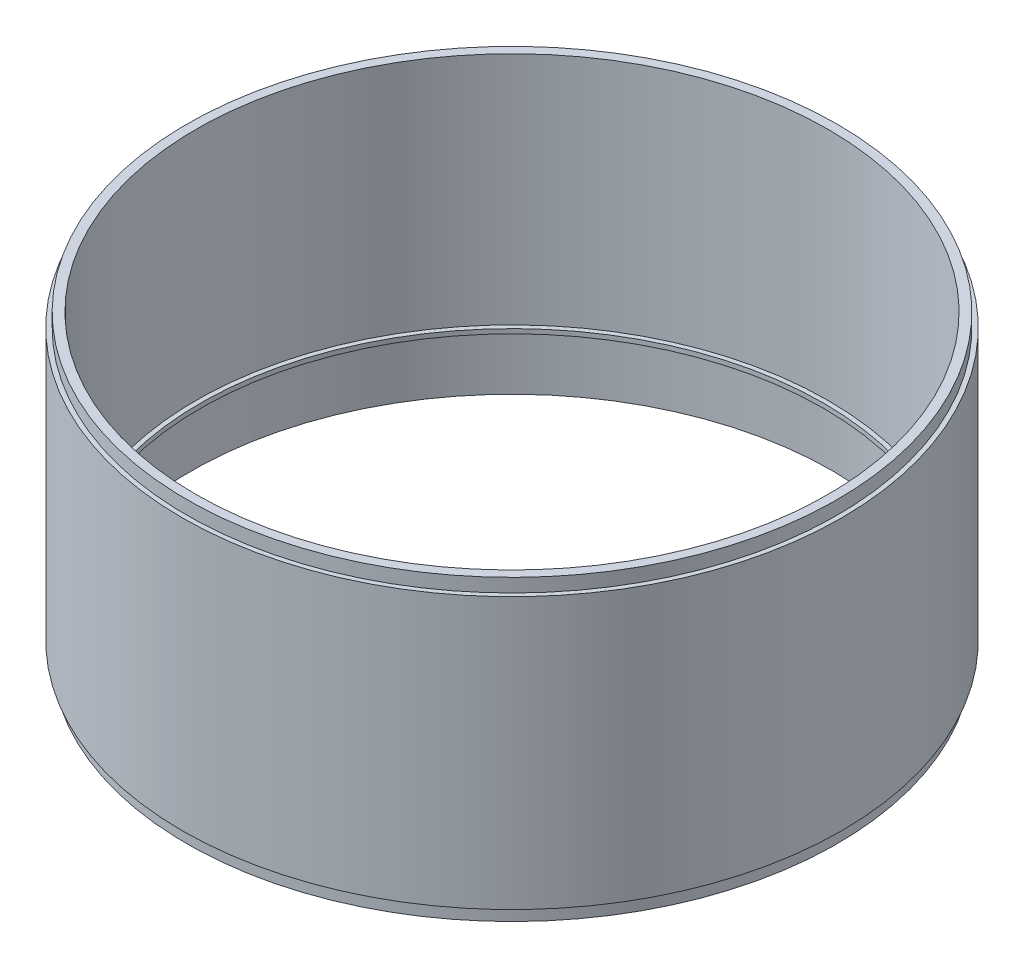
SolidWorks part; units mm, degrees
material "Silica Phenolic"
ref_plane "Piano frontale" through (0, 0, 0) normal (0, 0, 1) x (1, 0, 0)
ref_plane "Piano superiore" through (0, 0, 0) normal (0, 1, 0) x (1, 0, 0)
ref_plane "Piano destro" through (0, 0, 0) normal (1, 0, 0) x (0, 0, -1)
sketch "Schizzo1" plane through (0, 0, 0) normal (0, 0, 1) x (1, 0, 0)
  line L0 (-71, 3) -> (-71, 0)
  line L2 (-73, 3) -> (-73, 63)
  line L3 (-73, 63) -> (-72, 63)
  line L4 (-72, 63) -> (-72, 66)
  line L5 (-72, 66) -> (-70, 66)
  line L6 (-70, 66) -> (-70, 3)
  line L7 (-70, 3) -> (-71, 3)
  line L8 (0, 0) -> (0, 47.1479) construction
  line L9 (-71, 0) -> (-72, 0)
  line L10 (-72, 0) -> (-72, 3)
  line L11 (-72, 3) -> (-73, 3)
  line L12 (-71, 3) -> (-71, 13)
  line L13 (-71, 13) -> (-70, 13)
  line L14 (-70, 13) -> (-69, 13)
  line L15 (-69, 13) -> (-69, 14)
  line L16 (-69, 14) -> (-70, 14)
  dimension "D1" = 146
  dimension "D2" = 140
  dimension "D3" = 3
  dimension "D4" = 1
  dimension "D5" = 1
  dimension "D6" = 3
  dimension "D7" = 66
  dimension "D8" = 1
  dimension "D9" = 10
  dimension "D10" = 1
  dimension "D11" = 1
revolve "Rivoluzione1" add sketch "Schizzo1" angle 360 about L8 region at (-71.5391, 34.9246, 0) region at (-69.5, 13.5, 0)
